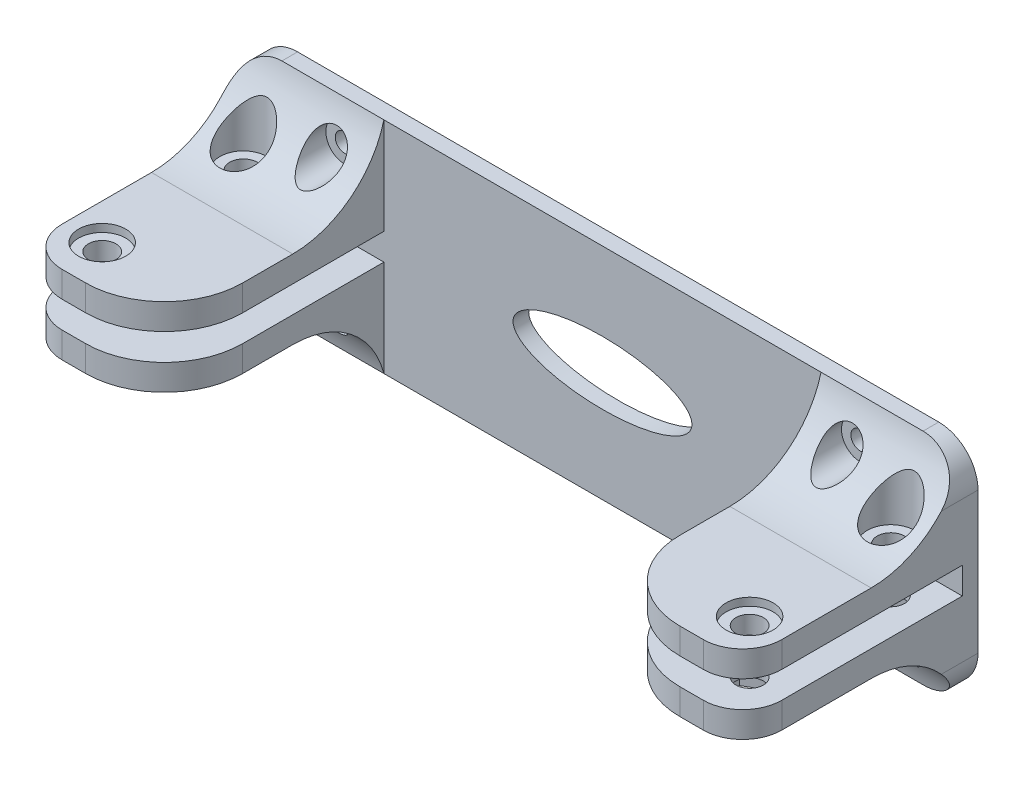
SolidWorks part; units mm, degrees
ref_plane "Front Plane" through (0, 0, 0) normal (0, 0, 1) x (1, 0, 0)
ref_plane "Top Plane" through (0, 0, 0) normal (0, 1, 0) x (1, 0, 0)
ref_plane "Right Plane" through (0, 0, 0) normal (1, 0, 0) x (0, 0, -1)
sketch "Sketch2" plane through (0, 0, 0) normal (0, 0, 1) x (1, 0, 0)
  line L0 (0, 14) -> (0, -14) construction
  line L1 (-45.85, -14) -> (45.85, -14)
  line L2 (-45.85, -14) -> (-45.85, 14)
  line L3 (-45.85, 14) -> (45.85, 14)
  line L4 (45.85, -14) -> (45.85, 14)
  line L5 (-45.85, -14) -> (45.85, 14) construction
  line L6 (-45.85, 14) -> (45.85, -14) construction
  circle A0 centre (-32.85, 9) radius 1.2
  circle A1 centre (-32.85, -9) radius 1.2
  circle A2 centre (32.85, -9) radius 1.2
  circle A3 centre (32.85, 9) radius 1.2
  point P0 (0, 0)
  dimension "D5" = 2.4
  dimension "D1" = 91.7
  dimension "D3" = 5
  dimension "D4" = 13
  dimension "D6" = 18
  dimension "D2" = 5
extrude "Boss-Extrude1" add sketch "Sketch2" along normal blind 2
sketch "Sketch3" plane through (-45.85, 0, 0) normal (-1, 0, 0) x (0, 0, 1)
  line L0 (0, 0) -> (22.146, 0) construction
  line L1 (0, 14) -> (0, -14) construction
  line L2 (2, 14) -> (2, -14) construction
  line L3 (30, 5) -> (2, 5)
  line L4 (30, 5) -> (30, -5)
  line L5 (30, -5) -> (2, -5)
  line L6 (2, 5) -> (2, -5)
  line L7 (30, 5) -> (2, -5) construction
  line L8 (30, -5) -> (2, 5) construction
  point P4 (16, 0)
  dimension "D1" = 28
  dimension "D2" = 10
extrude "Boss-Extrude2" add sketch "Sketch3" against normal blind 18
ref_plane "Plane1" through (0, 0, 0) normal (-1, 0, 0) x (0, 0, 1)
mirror "Mirror1" about plane through (0, 0, 0) normal (-1, 0, 0) of "Boss-Extrude2"
sketch "Sketch4" plane through (0, -5, 0) normal (0, -1, 0) x (1, 0, 0)
  line L0 (-27.85, 2) -> (-45.85, 2) construction
  line L1 (0, 0) -> (0, 31.6319) construction
  circle A0 centre (-41.25, 24.5) radius 1.75
  circle A1 centre (-41.25, 6.5) radius 1.75
  circle A2 centre (41.25, 6.5) radius 1.75
  circle A3 centre (41.25, 24.5) radius 1.75
  dimension "D1" = 3.5
  dimension "D2" = 18
  dimension "D3" = 4.5
  dimension "D4" = 82.5
extrude "Cut-Extrude1" cut sketch "Sketch4" against normal through all
fillet "Fillet3" radius 5 2 edges at (-45.85, 0, 30) (45.85, 0, 30)
fillet "Fillet4" radius 10 2 edges at (-27.85, 0, 30) (27.85, 0, 30)
sketch "Sketch5" plane through (0, 0, 30) normal (0, 0, 1) x (1, 0, 0)
  line L0 (-27.85, 0) -> (-45.85, 0) construction
  line L1 (-27.85, -5) -> (-27.85, 5) construction
  line L2 (-45.85, -5) -> (-45.85, 5) construction
  line L4 (-45.85, 1.7) -> (-27.85, 1.7)
  line L5 (-45.85, 1.7) -> (-45.85, -1.7)
  line L6 (-45.85, -1.7) -> (-27.85, -1.7)
  line L7 (-27.85, 1.7) -> (-27.85, -1.7)
  line L8 (-45.85, 1.7) -> (-27.85, -1.7) construction
  line L9 (-45.85, -1.7) -> (-27.85, 1.7) construction
  line L10 (39.5, -5) -> (43, -5)
  line L11 (39.5, -5) -> (43, -5)
  line L12 (39.5, -5) -> (43, -5)
  line L13 (39.5, -5) -> (43, -5)
  point P6 (-36.85, 0)
  point P13 (-41.25, -5)
  dimension "D1" = 3.4
  dimension "D4" = 4.6
  dimension "D2" = 0
  dimension "D3" = 0
extrude "Cut-Extrude2" cut sketch "Sketch5" against normal up to surface (28 mm away)
mirror "Mirror2" about plane through (0, 0, 0) normal (-1, 0, 0) of "Cut-Extrude2"
fillet "Fillet1" radius 12 4 edges at (36.85, -5, 2) (36.85, 5, 2)
sketch "Sketch6" plane through (0, 0, 2) normal (0, 0, 1) x (1, 0, 0)
  circle A0 centre (-32.85, 9) radius 2.4
  circle A1 centre (-32.85, -9) radius 2.4
  circle A2 centre (-32.85, -9) radius 1.2 construction
  circle A3 centre (32.85, -9) radius 2.4
  circle A4 centre (32.85, -9) radius 1.2 construction
  circle A5 centre (32.85, 9) radius 2.4
  circle A6 centre (32.85, 9) radius 1.2 construction
  dimension "D1" = 4.8
extrude "Cut-Extrude3" cut sketch "Sketch6" along normal through all
sketch "Sketch7" plane through (0, 0, 2) normal (0, 0, 1) x (1, 0, 0)
  ellipse E0 centre (0, 0) end of major axis (11.397, 0) minor radius 4.036
extrude "Cut-Extrude4" cut sketch "Sketch7" against normal through all
sketch "Sketch8" plane through (0, -5, 0) normal (0, -1, 0) x (1, 0, 0)
  line L0 (-45.85, 13.619) -> (-45.85, 25) construction
  line L1 (-41.25, 27.9641) -> (-44.25, 26.2321)
  line L2 (-44.25, 26.2321) -> (-44.25, 22.7679)
  line L3 (-44.25, 22.7679) -> (-41.25, 21.0359)
  line L4 (-41.25, 21.0359) -> (-38.25, 22.7679)
  line L5 (-38.25, 22.7679) -> (-38.25, 26.2321)
  line L6 (-38.25, 26.2321) -> (-41.25, 27.9641)
  line L8 (-41.25, 9.9641) -> (-44.25, 8.2321)
  line L9 (-44.25, 8.2321) -> (-44.25, 4.7679)
  line L10 (-44.25, 4.7679) -> (-41.25, 3.0359)
  line L11 (-41.25, 3.0359) -> (-38.25, 4.7679)
  line L12 (-38.25, 4.7679) -> (-38.25, 8.2321)
  line L13 (-38.25, 8.2321) -> (-41.25, 9.9641)
  circle A0 centre (-41.25, 24.5) radius 3 construction
  circle A1 centre (-41.25, 6.5) radius 3 construction
  dimension "D2" = 6
  dimension "D1" = 6
extrude "Cut-Extrude5" cut sketch "Sketch8" against normal blind 2 and the other way through all
mirror "Mirror3" about plane through (0, 0, 0) normal (-1, 0, 0) of "Cut-Extrude5"
sketch "Sketch9" plane through (0, 5, 0) normal (0, 1, 0) x (1, 0, 0)
  circle A0 centre (-41.25, -24.5) radius 3
  circle A1 centre (-41.25, -6.5) radius 3
  dimension "D1" = 6
extrude "Cut-Extrude6" cut sketch "Sketch9" against normal blind 1 and the other way through all
mirror "Mirror4" about plane through (0, 0, 0) normal (-1, 0, 0) of "Cut-Extrude6"
fillet "Fillet5" radius 5 4 edges at (-45.85, 14, 1) (-45.85, -14, 1) (45.85, -14, 1) (45.85, 14, 1)
equation "\"D2@Sketch2\"=\"D3@Sketch2\""
